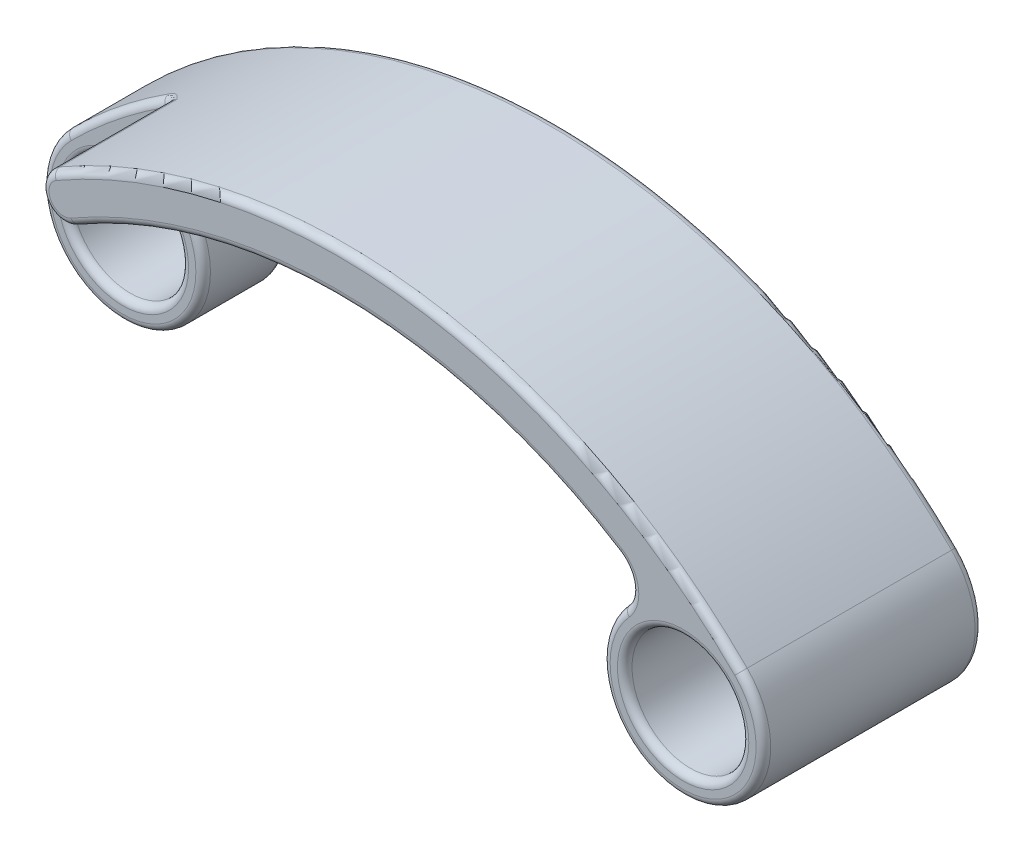
SolidWorks part; units mm, degrees
material "AR-M2"
ref_plane "正面" through (0, 0, 0) normal (0, 0, 1) x (1, 0, 0)
ref_plane "平面" through (0, 0, 0) normal (0, 1, 0) x (1, 0, 0)
ref_plane "右側面" through (0, 0, 0) normal (1, 0, 0) x (0, 0, -1)
sketch "ｽｹｯﾁ1" plane through (0, 0, 0) normal (0, 0, 1) x (1, 0, 0)
  circle A0 centre (23.6881, 23.6881) radius 4 construction
  circle A1 centre (-23.6881, 23.6881) radius 4 construction
  circle A2 centre (23.6881, 23.6881) radius 4
  circle A3 centre (-23.6881, 23.6881) radius 4
  circle A4 centre (-23.6881, 23.6881) radius 5.5
  circle A5 centre (23.6881, 23.6881) radius 5.5
  dimension "D1" = 11
extrude "ﾎﾞｽ - 押し出し1" add sketch "ｽｹｯﾁ1" along normal blind 15
sketch "ｽｹｯﾁ2" plane through (0, 0, 15) normal (0, 0, 1) x (1, 0, 0)
  circle A1 centre (-23.6881, 23.6881) radius 5.5
  circle A2 centre (-23.6881, 23.6881) radius 5.5
  dimension "D1" = 0
extrude "ｶｯﾄ - 押し出し1" cut sketch "ｽｹｯﾁ2" against normal blind 9
sketch "ｽｹｯﾁ4" plane through (0, 0, 0) normal (0, 0, -1) x (-1, 0, 0)
  arc A0 (27.5772, 27.5772) -> (-27.5772, 27.5772) centre (0, 0) ccw
  circle A1 centre (23.6881, 23.6881) radius 5.5 construction
  arc A2 (21.6205, 28.7846) -> (-21.6205, 28.7846) centre (0, 0) ccw
  circle A3 centre (-23.6881, 23.6881) radius 5.5 construction
  arc A5 (-21.6205, 28.7846) -> (-27.5772, 27.5772) centre (-23.6881, 23.6881) ccw
  arc A6 (27.5772, 27.5772) -> (21.6205, 28.7846) centre (23.6881, 23.6881) ccw
  dimension "D1" = 72
extrude "ﾎﾞｽ - 押し出し2" add sketch "ｽｹｯﾁ4" against normal up to surface (15 mm away) up to face at (29.1881, 23.6881, 15)
fillet "ﾌｨﾚｯﾄ1" radius 2 2 edges at (-21.6205, 28.7846, 3) (21.6205, 28.7846, 7.5)
fillet "ﾌｨﾚｯﾄ2" radius 1 1 edges at (-27.5772, 27.5772, 10.5)
sketch "ｽｹｯﾁ5" plane through (0, 0, 15) normal (0, 0, 1) x (1, 0, 0)
  line L0 (-18.75, 32.476) -> (0, 0) construction
  line L1 (0, 0) -> (0, 37.5) construction
  circle A0 centre (0, 0) radius 37.5 construction
  arc A1 (-19.5, 33.775) -> (-18, 31.1769) centre (-18.75, 32.476) ccw
  arc A2 (-18, 31.1769) -> (-21.6205, 28.7846) centre (0, 0) ccw
  arc A6 (27.5772, 27.5772) -> (-23.7214, 30.9564) centre (0, 0) ccw
  arc A7 (-23.7214, 30.9564) -> (-23.2016, 29.1665) centre (-23.1131, 30.1626) ccw
  arc A8 (-21.6205, 28.7846) -> (-23.2016, 29.1665) centre (-23.6881, 23.6881) ccw
  arc A9 (19.2204, 30.4397) -> (-21.6205, 28.7846) centre (0, 0) ccw
  arc A10 (19.6288, 27.3991) -> (19.2204, 30.4397) centre (18.1526, 28.7486) ccw
  arc A11 (19.6288, 27.3991) -> (27.5772, 27.5772) centre (23.6881, 23.6881) ccw
  arc A12 (-19.5, 33.775) -> (-23.7214, 30.9564) centre (0, 0) ccw
  arc A13 (-23.7214, 30.9564) -> (-23.2016, 29.1665) centre (-23.1131, 30.1626) ccw
  arc A14 (-21.6205, 28.7846) -> (-23.2016, 29.1665) centre (-23.6881, 23.6881) ccw
  dimension "D2" = 30
  dimension "D1" = 0
extrude "ｶｯﾄ - 押し出し2" cut sketch "ｽｹｯﾁ5" against normal up to surface (9 mm away) up to face at (-19.6881, 23.6881, 6)
fillet "ﾌｨﾚｯﾄ3" radius 0.5 19 edges at (-19.6881, 23.6881, 0) (-19.6881, 23.6881, 6) (27.6881, 23.6881, 15) (27.6881, 23.6881, 0) (0, 39, 0) (-23.8112, 18.1895, 0) (-23.8112, 18.1895, 6) (-20.1348, 29.0148, 6) (-20.1348, 29.0148, 0) (0, 36, 0) (20.1348, 29.0148, 15) (20.1348, 29.0148, 0) (23.8112, 18.1895, 15) (23.8112, 18.1895, 0) (-23.7417, 30.9408, 6) (-20.049, 31.726, 6) (5.0905, 38.6663, 15) (0.7129, 35.9929, 15) (-20.049, 31.726, 15)
